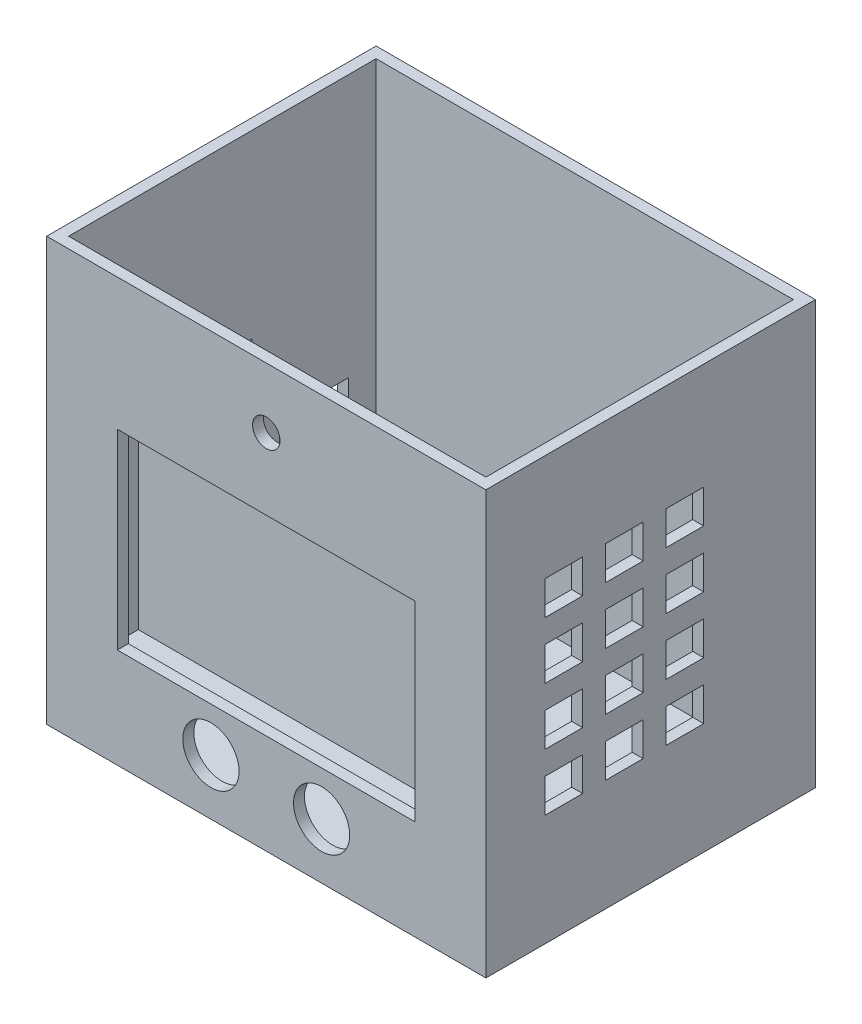
SolidWorks part; units mm, degrees
ref_plane "Front Plane" through (0, 0, 0) normal (0, 0, 1) x (1, 0, 0)
ref_plane "Top Plane" through (0, 0, 0) normal (0, 1, 0) x (1, 0, 0)
ref_plane "Right Plane" through (0, 0, 0) normal (1, 0, 0) x (0, 0, -1)
sketch "Sketch1" plane through (0, 0, 0) normal (0, 1, 0) x (1, 0, 0)
  line L1 (-50.8, 38.1) -> (50.8, 38.1)
  line L2 (-50.8, 38.1) -> (-50.8, -38.1)
  line L3 (-50.8, -38.1) -> (50.8, -38.1)
  line L4 (50.8, 38.1) -> (50.8, -38.1)
  line L5 (-50.8, 38.1) -> (50.8, -38.1) construction
  line L6 (-50.8, -38.1) -> (50.8, 38.1) construction
  point P0 (0, 0)
  dimension "D1" = 76.2
  dimension "D2" = 101.6
extrude "Boss-Extrude1" add sketch "Sketch1" along normal blind 97.79
ref_plane "Plane3" through (0, 0, 38.1) normal (0, 0, 1) x (1, 0, 0)
sketch "Sketch5" plane through (0, 0, 38.1) normal (0, 0, 1) x (1, 0, 0)
  line L0 (-50.8, 48.895) -> (50.8, 48.895) construction
  line L1 (-50.8, 97.79) -> (-50.8, 0) construction
  line L2 (50.8, 97.79) -> (50.8, 0) construction
  line L3 (0, 97.79) -> (0, 0) construction
  line L4 (-50.8, 97.79) -> (50.8, 97.79) construction
  line L6 (-34.4446, 67.31) -> (34.4446, 67.31)
  line L7 (-34.4446, 67.31) -> (-34.4446, 23.0772)
  line L8 (-34.4446, 23.0772) -> (34.4446, 23.0772)
  line L9 (34.4446, 67.31) -> (34.4446, 23.0772)
  line L10 (-34.4446, 67.31) -> (34.4446, 23.0772) construction
  line L11 (-34.4446, 23.0772) -> (34.4446, 67.31) construction
  point P11 (0, 48.895)
  point P12 (0, 45.1936)
  dimension "D1" = 68.8893
  dimension "D2" = 30.48
  dimension "D3" = 44.2328
extrude "Cut-Extrude3" cut sketch "Sketch5" against normal blind 2.54
shell "Shell1" thickness 2.54 removed face at (0, 45.1936, 35.56) removed face at (0, 97.79, 0)
ref_plane "Plane5" through (0, 0, 35.56) normal (0, 0, -1) x (-1, 0, 0)
sketch "Sketch7" plane through (0, 0, 35.56) normal (0, 0, -1) x (-1, 0, 0)
  line L0 (34.4446, 45.1936) -> (-34.4446, 45.1936) construction
  line L1 (34.4446, 67.31) -> (34.4446, 23.0772) construction
  line L2 (-34.4446, 23.0772) -> (-34.4446, 67.31) construction
  line L3 (0, 67.31) -> (0, 23.0772) construction
  line L4 (-34.4446, 67.31) -> (34.4446, 67.31) construction
  line L5 (34.4446, 23.0772) -> (-34.4446, 23.0772) construction
  line L6 (-50.8, 97.79) -> (50.8, 97.79) construction
  line L7 (37.592, 67.31) -> (-37.592, 67.31)
  line L8 (37.592, 67.31) -> (37.592, 21.59)
  line L9 (37.592, 21.59) -> (-37.592, 21.59)
  line L10 (-37.592, 67.31) -> (-37.592, 21.59)
  line L11 (37.592, 67.31) -> (-37.592, 21.59) construction
  line L12 (37.592, 21.59) -> (-37.592, 67.31) construction
  point P12 (0, 45.1936)
  point P13 (0, 44.45)
  dimension "D1" = 30.48
  dimension "D2" = 75.184
  dimension "D3" = 45.72
extrude "Boss-Extrude9" add sketch "Sketch7" along normal blind 5.461 separate body
shell "Shell3" thickness 2.54 removed face at (0, 44.45, 35.56) removed face at (0, 67.31, 32.8295) outward yes
sketch "Sketch8" plane through (0, 67.31, 0) normal (0, 1, 0) x (1, 0, 0)
  line L0 (37.592, -30.099) -> (37.592, -35.56) construction
  line L1 (37.592, -33.0069) -> (3.302, -33.0069)
  line L2 (37.592, -33.0069) -> (37.592, -22.7768)
  line L3 (37.592, -22.7768) -> (3.302, -22.7768)
  line L4 (3.302, -33.0069) -> (3.302, -22.7768)
  dimension "D1" = 34.29
extrude "Cut-Extrude4" cut sketch "Sketch8" against normal blind 6.35
ref_plane "Plane6" through (-50.8, 0, 0) normal (1, 0, 0) x (0, 0, -1)
sketch "Sketch9" plane through (-50.8, 0, 53.34) normal (-1, 0, 0) x (0, 0, 1)
  line L1 (-82.55, 4.572) -> (-66.548, 4.572)
  line L2 (-82.55, 4.572) -> (-82.55, 19.3675)
  line L3 (-82.55, 19.3675) -> (-66.548, 19.3675)
  line L4 (-66.548, 4.572) -> (-66.548, 19.3675)
  line L8 (-91.44, 97.79) -> (-91.44, 0) construction
  line L9 (-91.44, 0) -> (-15.24, 0) construction
  line L11 (-82.55, 22.2885) -> (-66.548, 22.2885)
  line L12 (-82.55, 22.2885) -> (-82.55, 37.084)
  line L13 (-82.55, 37.084) -> (-66.548, 37.084)
  line L14 (-66.548, 22.2885) -> (-66.548, 37.084)
  dimension "D1" = 8.89
  dimension "D2" = 16.002
  dimension "D3" = 14.7955
  dimension "D4" = 4.572
  dimension "D5" = 2.921
  dimension "D6" = 14.7955
extrude "Cut-Extrude6" cut sketch "Sketch9" against normal blind 2.54
sketch "Sketch13" plane through (0, 2.54, 0) normal (0, 1, 0) x (1, 0, 0)
  line L0 (-48.26, 0) -> (48.26, 0) construction
  line L1 (-48.26, 35.56) -> (-48.26, -35.56) construction
  line L2 (48.26, -35.56) -> (48.26, 35.56) construction
  line L3 (0, 35.56) -> (0, -35.56) construction
  line L4 (48.26, 35.56) -> (-48.26, 35.56) construction
  line L5 (52.3875, -35.56) -> (-52.3875, -35.56) construction
  line L7 (-15.76, 6.35) -> (7.1, 6.35)
  line L8 (-15.76, 6.35) -> (-15.76, -6.35)
  line L9 (-15.76, -6.35) -> (7.1, -6.35)
  line L10 (7.1, 6.35) -> (7.1, -6.35)
  line L11 (-15.76, 6.35) -> (7.1, -6.35) construction
  line L12 (-15.76, -6.35) -> (7.1, 6.35) construction
  point P13 (-4.33, 0)
  dimension "D1" = 12.7
  dimension "D2" = 22.86
  dimension "D3" = 4.33
extrude "Cut-Extrude8" cut sketch "Sketch13" against normal blind 2.54
sketch "Sketch14" plane through (0, 0, 38.1) normal (0, 0, 1) x (1, 0, 0)
  line L0 (0, 0) -> (0, 23.0772) construction
  line L1 (-34.4446, 23.0772) -> (34.4446, 23.0772) construction
  line L2 (-12.8, 12.84) -> (12.8, 12.84) construction
  line L3 (-50.8, 0) -> (50.8, 0) construction
  circle A0 centre (-12.8, 12.84) radius 6.5
  circle A1 centre (12.8, 12.84) radius 6.5
  point P8 (0, 11.5386)
  dimension "D2" = 13
  dimension "D3" = 12.84
  dimension "D1" = 25.6
extrude "Cut-Extrude10" cut sketch "Sketch14" against normal blind 12.7
sketch "Sketch16" plane through (0, 0, 38.1) normal (0, 0, 1) x (1, 0, 0)
  line L0 (0, 97.79) -> (0, 67.31) construction
  line L1 (-50.8, 97.79) -> (50.8, 97.79) construction
  line L2 (34.4446, 67.31) -> (-34.4446, 67.31) construction
  circle A0 centre (0, 83.82) radius 3.175
  point P6 (0, 83.82)
  dimension "D1" = 6.35
  dimension "D2" = 13.97
extrude "Cut-Extrude11" cut sketch "Sketch16" against normal blind 2.54
ref_plane "Plane7" through (50.8, 0, 0) normal (1, 0, 0) x (0, 0, -1)
sketch "Sketch17" plane through (50.8, 0, 0) normal (1, 0, 0) x (0, 0, -1)
  line L1 (-24.4499, 73.1623) -> (-15.7299, 73.1623)
  line L2 (-24.4499, 73.1623) -> (-24.4499, 65.3623)
  line L3 (-24.4499, 65.3623) -> (-15.7299, 65.3623)
  line L4 (-15.7299, 73.1623) -> (-15.7299, 65.3623)
  dimension "D1" = 7.8
  dimension "D2" = 8.7201
extrude "Cut-Extrude12" cut sketch "Sketch17" against normal blind 2.54
pattern_linear "LPattern1" count 3 spacing 14 along (0, 0, -1) count 4 spacing 13.2 along (0, -1, 0) of "Cut-Extrude12"
sketch "Sketch18" plane through (-50.8, 0, 0) normal (1, 0, 0) x (0, 0, -1)
  line L0 (38.1, 97.79) -> (38.1, 0) construction
  line L1 (38.1, 0) -> (-38.1, 0) construction
  circle A0 centre (6.35, 54.61) radius 0.3175
  circle A1 centre (5.08, 51.435) radius 0.3175
  dimension "D1" = 31.75
  dimension "D2" = 0.635
  dimension "D3" = 54.61
  dimension "D4" = 0.635
  dimension "D5" = 3.175
  dimension "D6" = 1.27
extrude "Cut-Extrude13" cut sketch "Sketch18" along normal blind 2.54
pattern_linear "LPattern2" count 11 spacing 2.54 along (0, 0, 1) count 7 spacing 6.35 along (0, -1, 0) of "Cut-Extrude13"
sketch "Sketch12" plane through (-50.8, 0, 0) normal (-1, 0, 0) x (0, 0, 1)
  line L1 (-6.858, 56.0036) -> (21.082, 56.0036)
  line L2 (-6.858, 56.0036) -> (-6.858, 12.8236)
  line L3 (-6.858, 12.8236) -> (21.082, 12.8236)
  line L4 (21.082, 56.0036) -> (21.082, 12.8236)
  line L5 (-6.858, 56.0036) -> (21.082, 12.8236) construction
  line L6 (-6.858, 12.8236) -> (21.082, 56.0036) construction
  line L7 (-13.208, 4.572) -> (-13.208, 19.3675) construction
  line L8 (-38.1, 0) -> (38.1, 0) construction
  point P0 (7.112, 34.4136)
  dimension "D1" = 27.94
  dimension "D2" = 43.18
  dimension "D3" = 6.35
  dimension "D4" = 12.8236
extrude "Cut-Extrude7" cut sketch "Sketch12" against normal blind 2.54 contours L2 L1 L4 L3
